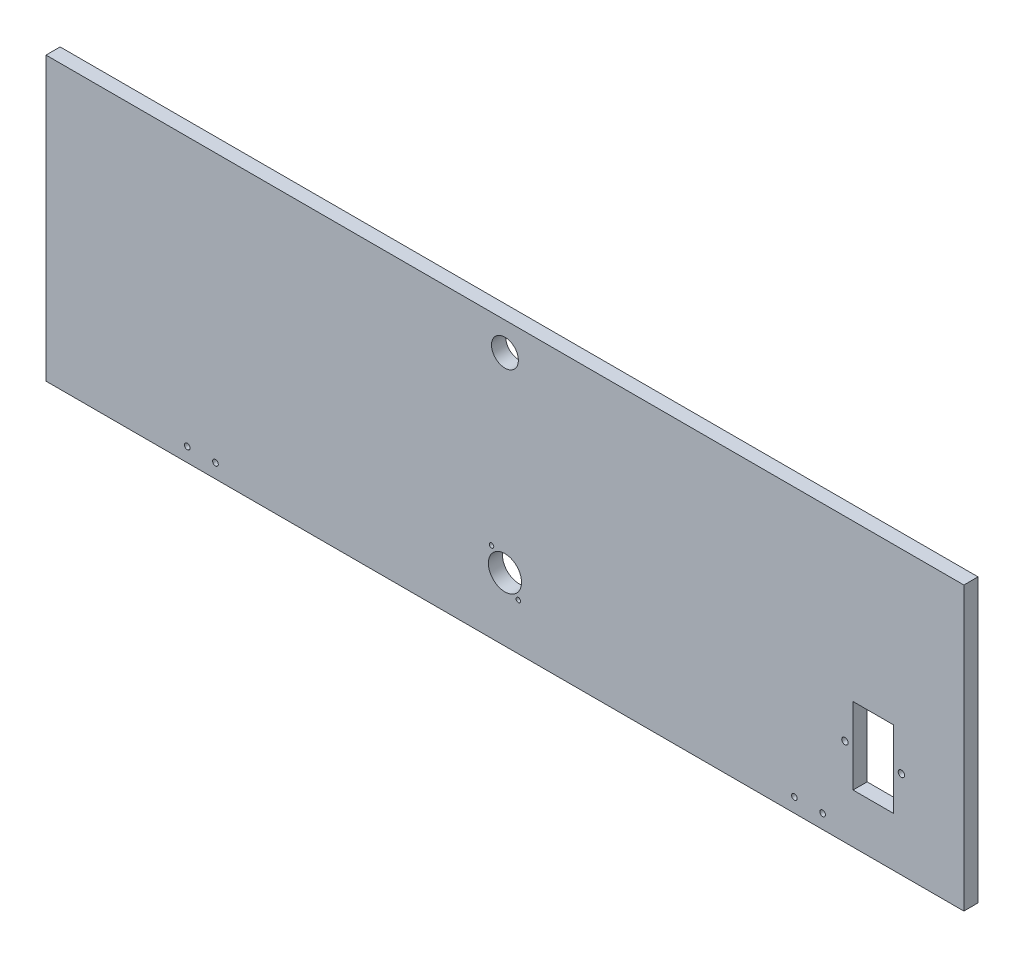
SolidWorks part; units mm, degrees
ref_plane "Plan de face" through (0, 0, 0) normal (0, 0, 1) x (1, 0, 0)
ref_plane "Plan de dessus" through (0, 0, 0) normal (0, 1, 0) x (1, 0, 0)
ref_plane "Plan de droite" through (0, 0, 0) normal (1, 0, 0) x (0, 0, -1)
sketch "Esquisse1" plane through (0, 0, 0) normal (0, 0, 1) x (1, 0, 0)
  line L1 (0, 0) -> (650, 0)
  line L2 (0, 0) -> (0, 200)
  line L3 (0, 200) -> (650, 200)
  line L4 (650, 0) -> (650, 200)
  dimension "D1" = 200
  dimension "D2" = 650
extrude "Boss.-Extru.1" add sketch "Esquisse1" along normal blind 10
sketch "Esquisse2" plane through (0, 0, 10) normal (0, 0, 1) x (1, 0, 0)
  line L4 (0, 200) -> (0, 0) construction
  line L5 (650, 0) -> (650, 200) construction
  line L6 (0, 0) -> (650, 0) construction
  circle A0 centre (100, 10) radius 2
  circle A1 centre (120, 10) radius 2
  circle A2 centre (530, 10) radius 2
  circle A3 centre (550, 10) radius 2
  dimension "D1" = 4
  dimension "D2" = 4
  dimension "D3" = 4
  dimension "D4" = 4
  dimension "D5" = 20
  dimension "D6" = 20
  dimension "D7" = 100
  dimension "D8" = 100
  dimension "D9" = 10
  dimension "D10" = 10
  dimension "D11" = 10
  dimension "D12" = 10
extrude "Enlèv. mat.-Extru.1" cut sketch "Esquisse2" against normal blind 10
sketch "Esquisse3" plane through (0, 0, 10) normal (0, 0, 1) x (1, 0, 0)
  line L0 (0, 0) -> (650, 0) construction
  line L1 (334.5004, 33.0006) -> (325, 45)
  line L2 (325, 45) -> (315.4996, 56.9994)
  line L3 (325, 45) -> (265.8175, 45)
  line L4 (325, 45) -> (364.3682, 45)
  line L5 (650, 0) -> (650, 200) construction
  line L6 (571.5, 35) -> (600, 35)
  line L7 (571.5, 35) -> (571.5, 89.3)
  line L8 (571.5, 89.3) -> (600, 89.3)
  line L9 (600, 35) -> (600, 89.3)
  circle A0 centre (325, 45) radius 11.75
  circle A1 centre (315.4996, 56.9994) radius 1.6
  circle A2 centre (334.5004, 33.0006) radius 1.6
  circle A3 centre (565.75, 62.15) radius 2.25
  circle A4 centre (605.75, 62.15) radius 2.25
  point P4 (325, 0)
  point P19 (585.75, 89.3)
  point P20 (571.5, 62.15)
  point P21 (0, 0)
  dimension "D1" = 23.5
  dimension "D4" = 3.2
  dimension "D5" = 3.2
  dimension "D14" = 4.5
  dimension "D15" = 4.5
  dimension "D2" = 0
  dimension "D3" = 45
  dimension "D6" = 30.61
  dimension "D7" = 15.305
  dimension "D8" = 51.63
  dimension "D9" = 180
  dimension "D10" = 51.63
  dimension "D11" = 15.305
  dimension "D12" = 28.5
  dimension "D13" = 54.3
  dimension "D16" = 40
  dimension "D17" = 20
  dimension "D18" = 0
  dimension "D19" = 35
  dimension "D20" = 50
  dimension "D21" = 20
extrude "Enlèv. mat.-Extru.2" cut sketch "Esquisse3" against normal blind 10 contours L3 A0 L1 | L4 A0 L2 | L1 A0 L4 | L2 A0 L3 | A1 | A2 | L6 L9 L8 L7 | A3 | A4 region at (314.1, 57.6764, 10) region at (322.2589, 39.3335, 10) region at (331.8154, 41.7031, 10) region at (335.1774, 34.4002, 10) region at (318.1846, 48.2969, 10) region at (327.7411, 50.6665, 10) region at (585.75, 62.15, 10)
sketch "Esquisse4" plane through (0, 0, 10) normal (0, 0, 1) x (1, 0, 0)
  line L0 (650, 200) -> (0, 200) construction
  circle A0 centre (325, 180) radius 9.5
  point P4 (325, 200)
  point P7 (0, 0)
  dimension "D1" = 19
  dimension "D3" = 20
  dimension "D2" = 0
extrude "Enlèv. mat.-Extru.3" cut sketch "Esquisse4" against normal blind 10
sketch "Esquisse5" plane through (0, 0, 0) normal (0, 0, 1) x (1, 0, 0)
  line L0 (650, 200) -> (0, 200) construction
  circle A0 centre (341, 180) radius 1.5
  circle A1 centre (309, 180) radius 1.5
  point P6 (325, 200)
  dimension "D2" = 3
  dimension "D3" = 3
  dimension "D1" = 32
  dimension "D4" = 16
  dimension "D5" = 20
  dimension "D6" = 20
extrude "Enlèv. mat.-Extru.4" cut sketch "Esquisse5" along normal blind 2
